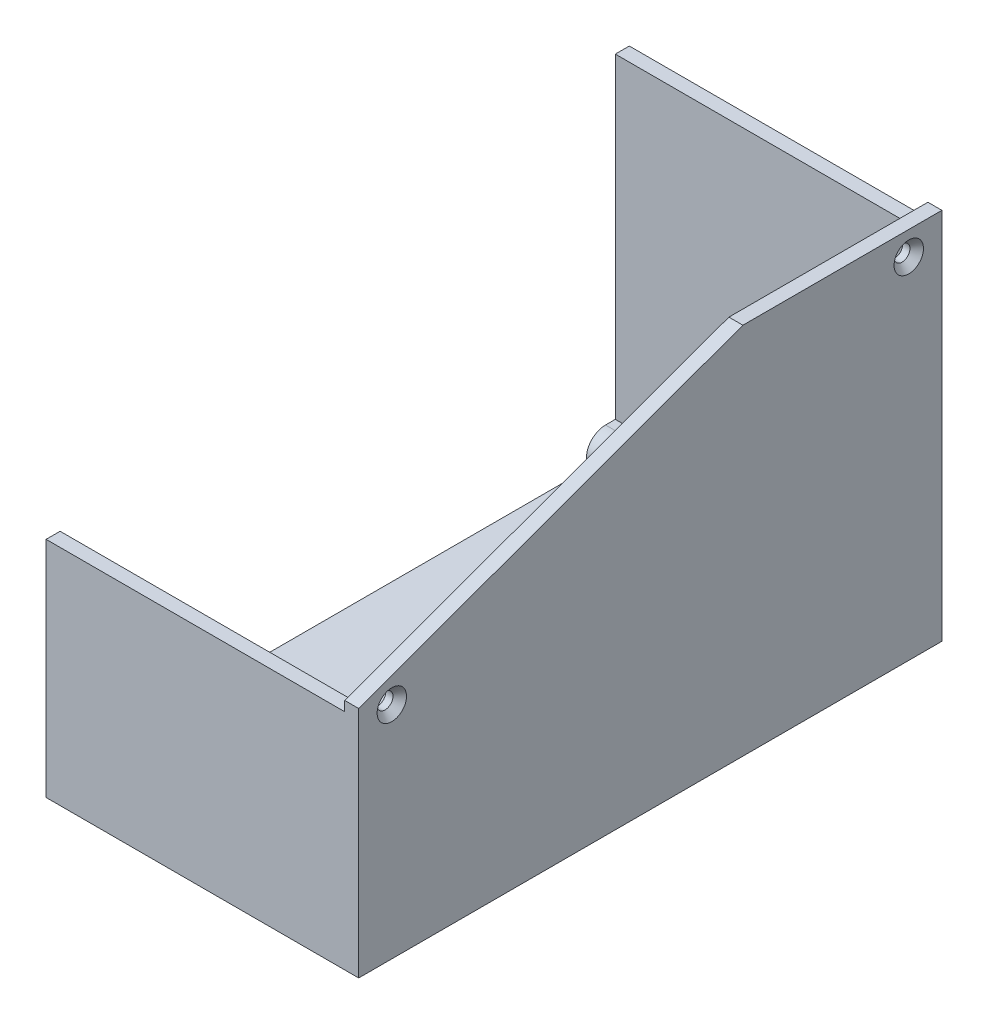
SolidWorks part; units mm, degrees
ref_plane "Спереди" through (0, 0, 0) normal (0, 0, 1) x (1, 0, 0)
ref_plane "Сверху" through (0, 0, 0) normal (0, 1, 0) x (1, 0, 0)
ref_plane "Справа" through (0, 0, 0) normal (1, 0, 0) x (0, 0, -1)
sketch "Эскиз18" plane through (0, 0, 0) normal (1, 0, 0) x (0, 0, -1)
  line L0 (53.75, 71) -> (53.75, -6)
  line L1 (53.75, -6) -> (-71.25, -6)
  line L2 (-71.25, -6) -> (-71.25, 41.9283)
  line L3 (-68.25, 41.9283) -> (-68.25, -3)
  line L4 (-68.25, -3) -> (50.75, -3)
  line L5 (50.75, -3) -> (50.75, 71)
  line L6 (50.75, 71) -> (53.75, 71)
  line L7 (-71.25, 41.9283) -> (-68.25, 41.9283)
  line L8 (50.75, -3) -> (50.75, -6) construction
  line L9 (-68.25, -3) -> (-68.25, -6) construction
  line L10 (-41.25, 0) -> (41.25, 0) construction
  line L11 (-41.25, 21) -> (-41.25, 3) construction
  line L12 (-71.25, 41.9283) -> (-68.25, 41.9283) construction
  dimension "D1" = 3
  dimension "D2" = 3
  dimension "D3" = 27
  dimension "D4" = 125
  dimension "D5" = 77
extrude "Бобышка-Вытянуть1" add sketch "Эскиз18" along normal mid plane 64
sketch "Эскиз19" plane through (32, 0, 0) normal (1, 0, 0) x (0, 0, -1)
  line L0 (-71.25, 44.0289) -> (11.0949, 74)
  line L1 (11.0949, 74) -> (53.75, 74)
  line L8 (53.75, 71) -> (50.75, 71)
  line L9 (50.75, 71) -> (50.75, -3)
  line L10 (50.75, -3) -> (-68.25, -3)
  line L11 (-68.25, -3) -> (-68.25, 41.9283)
  line L12 (-68.25, 41.9283) -> (-71.25, 41.9283)
  line L13 (-71.25, 41.9283) -> (-71.25, -6)
  line L14 (-71.25, -6) -> (53.75, -6)
  line L15 (53.75, -6) -> (53.75, 71)
  line L21 (-71.25, 44.0289) -> (-71.25, -6)
  line L22 (-71.25, -6) -> (53.75, -6)
  line L23 (53.75, -6) -> (53.75, 74)
  dimension "D1" = 0
extrude "Бобышка-Вытянуть2" add sketch "Эскиз19" along normal blind 3
sketch "Эскиз20" plane through (-32, 0, 0) normal (-1, 0, 0) x (0, 0, 1)
  line L0 (-53.75, 3.2) -> (-48.65, 3.2)
  line L1 (-53.75, -6) -> (-53.75, 71) construction
  line L2 (-44.55, -0.9) -> (-44.55, -6)
  line L3 (71.25, -6) -> (-53.75, -6) construction
  line L4 (-44.55, -6) -> (-53.75, -6)
  line L5 (-53.75, -6) -> (-53.75, 3.2)
  line L7 (71.25, -6) -> (62.05, -6)
  line L8 (62.05, -6) -> (62.05, -0.9)
  line L9 (66.15, 3.2) -> (71.25, 3.2)
  line L10 (71.25, 41.9283) -> (71.25, -6) construction
  line L11 (71.25, 3.2) -> (71.25, -6)
  arc A0 (-48.65, 3.2) -> (-44.55, -0.9) centre (-48.65, -0.9) cw
  circle A1 centre (-48.65, -0.9) radius 2.1
  arc A2 (62.05, -0.9) -> (66.15, 3.2) centre (66.15, -0.9) cw
  circle A3 centre (66.15, -0.9) radius 2.1
  line M8 (-53.75, 71) -> (-53.75, -6)
  line M9 (-53.75, -6) -> (71.25, -6)
  line M10 (71.25, -6) -> (71.25, 41.9283)
  line M12 (68.25, 41.9283) -> (68.25, -3)
  line M13 (68.25, -3) -> (-50.75, -3)
  line M14 (-50.75, -3) -> (-50.75, 71)
  dimension "D1" = 2
  dimension "D2" = 4.2
  dimension "D3" = 3
  dimension "D4" = 3
extrude "Бобышка-Вытянуть3" add sketch "Эскиз20" against normal blind 6 contours A1 L2 A0 L0 M13 M14 | A1 | L2 L0 M13 M14 M8 M9 | A1 M14 M13 | L9 L8 M12 M13 M9 M10 | A3 L9 A2 L8 M12 M13 | A3 M13 M12 | A3 region at (-32, 3.0699, -52.25) region at (-32, 3.1123, -49.7) region at (-32, -0.9, -48.65) region at (-32, -2.5309, -50.2809) region at (-32, -4.5, 62.1801) region at (-32, -1.95, 62.1377) region at (-32, -0.9, 66.15) region at (-32, -2.5309, 67.7809)
extrude "Вырез-Вытянуть1" cut sketch "Эскиз20<3>" against normal blind 4 contours A1 | A3 region at (-32, -0.9, -48.65) region at (-32, -0.9, 66.15)
sketch "Эскиз20<3>" plane through (-32, 0, 0) normal (-1, 0, 0) x (0, 0, 1) same geometry as "Эскиз20"
hole_wizard "Зенковка для винта с потайной головкой M32" positions "Эскиз31" profile "Эскиз32" countersink size "M3" standard "DIN" end condition through all
sketch "Эскиз31" plane through (35, 0, 0) normal (1, 0, 0) x (0, 0, -1)
  point P3 (-64.15, 41.1858)
  point P7 (46.65, 68.9)
sketch "Эскиз32" plane through (35, 41.1858, 64.15) normal (0, 1, 0) x (0, 0, -1)
  line L0 (0, 0) -> (0, 67)
  line L1 (0, 67) -> (1.7, 67)
  line L2 (1.7, 67) -> (1.7, 1.45)
  line L3 (1.7, 1.45) -> (3.15, 0)
  line L5 (3.15, 0) -> (0, 0)
  line L6 (-1.7, 1.45) -> (-3.15, 0) construction
  line L11 (0, -6.35) -> (0, 107.95) construction
  dimension "Диаметр сквозного отверстия" = 3.4
  dimension "Глубина сквозного отверстия" = 67
  dimension "Диаметр передней зенковки" = 6.3
  dimension "Угол передней зенковки" = 90
ref_plane "Плоскость1" through (0, -16.8594, 46.3209) normal (0, -0.342, 0.9397) x (1, 0, 0)
